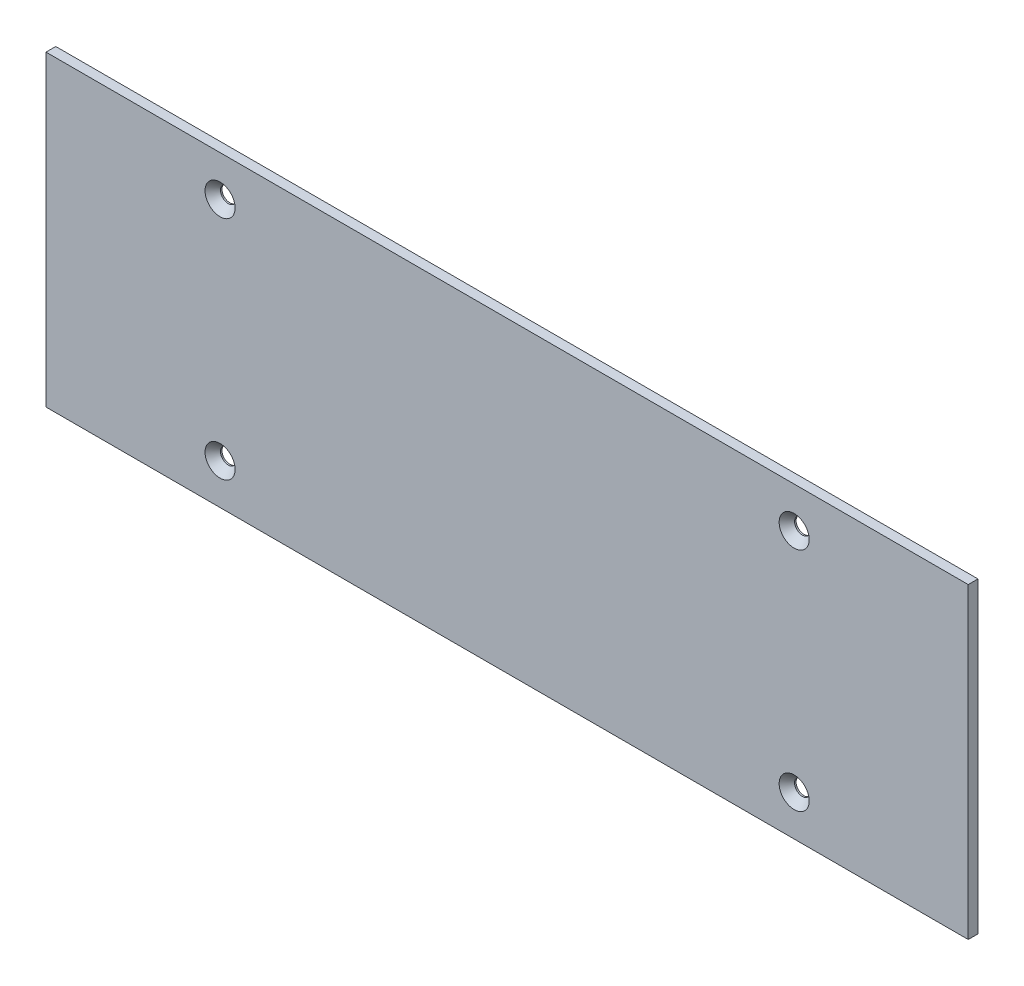
SolidWorks part; units mm, degrees
material "6061 Alloy"
ref_plane "Front Plane" through (0, 0, 0) normal (0, 0, 1) x (1, 0, 0)
ref_plane "Top Plane" through (0, 0, 0) normal (0, 1, 0) x (1, 0, 0)
ref_plane "Right Plane" through (0, 0, 0) normal (1, 0, 0) x (0, 0, -1)
sketch "Sketch1" plane through (0, 0, 0) normal (0, 0, 1) x (1, 0, 0)
  line L1 (-150, -50) -> (150, -50)
  line L2 (-150, -50) -> (-150, 50)
  line L3 (-150, 50) -> (150, 50)
  line L4 (150, -50) -> (150, 50)
  line L5 (-150, -50) -> (150, 50) construction
  line L6 (-150, 50) -> (150, -50) construction
  point P0 (0, 0)
  dimension "D1" = 100
  dimension "D2" = 300
extrude "Boss-Extrude1" add sketch "Sketch1" along normal blind 3.175
sketch "Sketch2" plane through (0, 0, 3.175) normal (0, 0, 1) x (1, 0, 0)
  point P0 (93.375, 36.825)
  point P1 (-93.375, 36.825)
  point P3 (-93.375, -36.825)
  point P5 (93.375, -36.825)
hole_wizard "CSK for #10 Flat Head Machine Screw1" positions "Sketch2" profile "Sketch3" countersink size "#10" standard "ANSI Inch"
sketch "Sketch3" plane through (93.375, 36.825, 3.175) normal (1, 0, 0) x (0, -1, 0)
  line L0 (0, 0) -> (0, 6.3598)
  line L1 (0, 6.3598) -> (2.5527, 4.826)
  line L2 (2.5527, 4.826) -> (2.5527, 2.6882)
  line L3 (2.5527, 2.6882) -> (4.8895, 0)
  line L5 (4.8895, 0) -> (0, 0)
  line L6 (-2.5527, 2.6882) -> (-4.8895, 0) construction
  line L10 (0, 6.3598) -> (-2.5527, 4.826) construction
  line L11 (0, -6.35) -> (0, 107.95) construction
  dimension "Hole Dia." = 5.1054
  dimension "Hole Depth" = 4.826
  dimension "Near C'Sink Dia." = 9.779
  dimension "Near C'Sink Angle" = 82
  dimension "Drill Angle" = 118
equation "\"side\"= 100mm"
equation "\"thk\"= 1 / 8"
equation "\"D1@Sketch1\"=\"side\""
equation "\"D2@Sketch1\"=\"side\"*3"
equation "\"D1@Boss-Extrude1\"=\"thk\""
